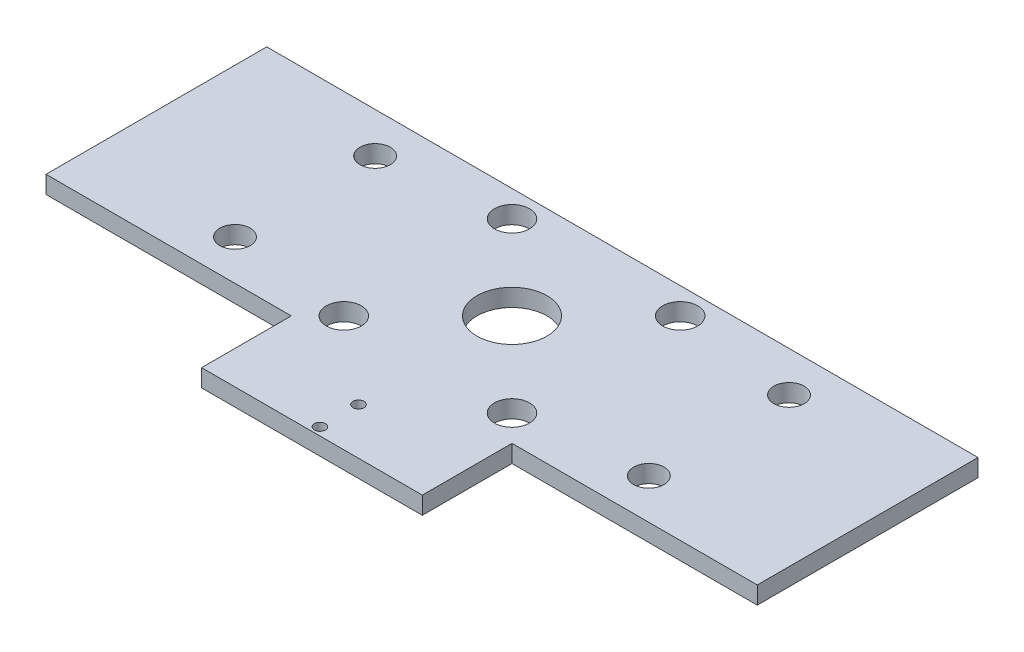
SolidWorks part; units mm, degrees
ref_plane "Front Plane" through (0, 0, 0) normal (0, 0, 1) x (1, 0, 0)
ref_plane "Top Plane" through (0, 0, 0) normal (0, 1, 0) x (1, 0, 0)
ref_plane "Right Plane" through (0, 0, 0) normal (1, 0, 0) x (0, 0, -1)
sketch "Sketch1" plane through (0, 0, 0) normal (0, 1, 0) x (1, 0, 0)
  line L0 (40, -40) -> (128.9, -40)
  line L1 (-128.9, 40) -> (128.9, 40)
  line L2 (-128.9, 40) -> (-128.9, -40)
  line L3 (-128.9, -40) -> (-40, -40)
  line L4 (128.9, 40) -> (128.9, -40)
  line L5 (-128.9, 40) -> (128.9, -40) construction
  line L6 (-128.9, -40) -> (128.9, 40) construction
  line L8 (-40, -40) -> (-40, -72.5)
  line L9 (-40, -72.5) -> (40, -72.5)
  line L10 (40, -40) -> (40, -72.5)
  point P0 (0, 0)
  point P10 (0, -72.5)
  dimension "D1" = 80
  dimension "D2" = 257.8
  dimension "D3" = 80
  dimension "D4" = 72.5
extrude "Boss-Extrude1" add sketch "Sketch1" along normal mid plane 6.35
hole_wizard "1 (1) Diameter Hole1" positions "Sketch3" profile "Sketch2" hole size "1" standard "ANSI Inch" end condition through all
sketch "Sketch3" plane through (0, 3.175, 0) normal (0, 1, 0) x (1, 0, 0)
  point P0 (0, 0)
sketch "Sketch2" plane through (0, 3.175, 0) normal (1, 0, 0) x (0, 0, 1)
  line L0 (0, 0) -> (0, 6.35)
  line L1 (0, 6.35) -> (12.7, 6.35)
  line L2 (12.7, 6.35) -> (12.7, 0)
  line L5 (12.7, 0) -> (0, 0)
  line L11 (0, -6.35) -> (0, 107.95) construction
  dimension "Thru Hole Dia." = 25.4
  dimension "Thru Hole Depth" = 6.35
hole_wizard "1/2 (0.5) Diameter Hole1" positions "Sketch5" profile "Sketch4" hole size "1/2" standard "ANSI Inch" end condition through all
sketch "Sketch5" plane through (0, 3.175, 0) normal (0, 1, 0) x (1, 0, 0)
  line L1 (-30.48, 30.48) -> (30.48, 30.48)
  line L2 (-30.48, 30.48) -> (-30.48, -30.48)
  line L3 (-30.48, -30.48) -> (30.48, -30.48)
  line L4 (30.48, 30.48) -> (30.48, -30.48)
  line L5 (-30.48, 30.48) -> (30.48, -30.48) construction
  line L6 (-30.48, -30.48) -> (30.48, 30.48) construction
  point P2 (30.48, -30.48)
  point P5 (-30.48, 30.48)
  point P6 (-30.48, -30.48)
  point P7 (30.48, 30.48)
  dimension "D1" = 60.96
sketch "Sketch4" plane through (30.48, 3.175, 30.48) normal (1, 0, 0) x (0, 0, 1)
  line L0 (0, 0) -> (0, 6.35)
  line L1 (0, 6.35) -> (6.35, 6.35)
  line L2 (6.35, 6.35) -> (6.35, 0)
  line L5 (6.35, 0) -> (0, 0)
  line L11 (0, -6.35) -> (0, 107.95) construction
  dimension "Thru Hole Dia." = 12.7
  dimension "Thru Hole Depth" = 6.35
hole_wizard "Ø4.0 (4) Diameter Hole1" positions "Sketch7" profile "Sketch6" hole size "Ø4.0" standard "ANSI Metric" end condition through all
sketch "Sketch7" plane through (0, 3.175, 0) normal (0, 1, 0) x (1, 0, 0)
  point P0 (0, -55.63)
  point P2 (0, -69.63)
  dimension "D1" = 55.63
  dimension "D2" = 14
sketch "Sketch6" plane through (0, 3.175, 55.63) normal (1, 0, 0) x (0, 0, 1)
  line L0 (0, 0) -> (0, 6.35)
  line L1 (0, 6.35) -> (2, 6.35)
  line L2 (2, 6.35) -> (2, 0)
  line L5 (2, 0) -> (0, 0)
  line L11 (0, -6.35) -> (0, 107.95) construction
  dimension "Thru Hole Dia." = 4
  dimension "Thru Hole Depth" = 6.35
hole_wizard "M10 Clearance Hole1" positions "Sketch9" profile "Sketch8" hole size "M10" standard "ANSI Metric" end condition through all
sketch "Sketch9" plane through (0, 3.175, 0) normal (0, 1, 0) x (1, 0, 0)
  line L1 (-75, 25.4) -> (75, 25.4)
  line L2 (-75, 25.4) -> (-75, -25.4)
  line L3 (-75, -25.4) -> (75, -25.4)
  line L4 (75, 25.4) -> (75, -25.4)
  line L5 (-75, 25.4) -> (75, -25.4) construction
  line L6 (-75, -25.4) -> (75, 25.4) construction
  point P2 (75, -25.4)
  point P5 (-75, 25.4)
  point P6 (-75, -25.4)
  point P7 (75, 25.4)
  dimension "D1" = 50.8
  dimension "D2" = 150
sketch "Sketch8" plane through (75, 3.175, 25.4) normal (1, 0, 0) x (0, 0, 1)
  line L0 (0, 0) -> (0, 6.35)
  line L1 (0, 6.35) -> (5.5, 6.35)
  line L2 (5.5, 6.35) -> (5.5, 0)
  line L5 (5.5, 0) -> (0, 0)
  line L11 (0, -6.35) -> (0, 107.95) construction
  dimension "Thru Hole Dia." = 11
  dimension "Thru Hole Depth" = 6.35
